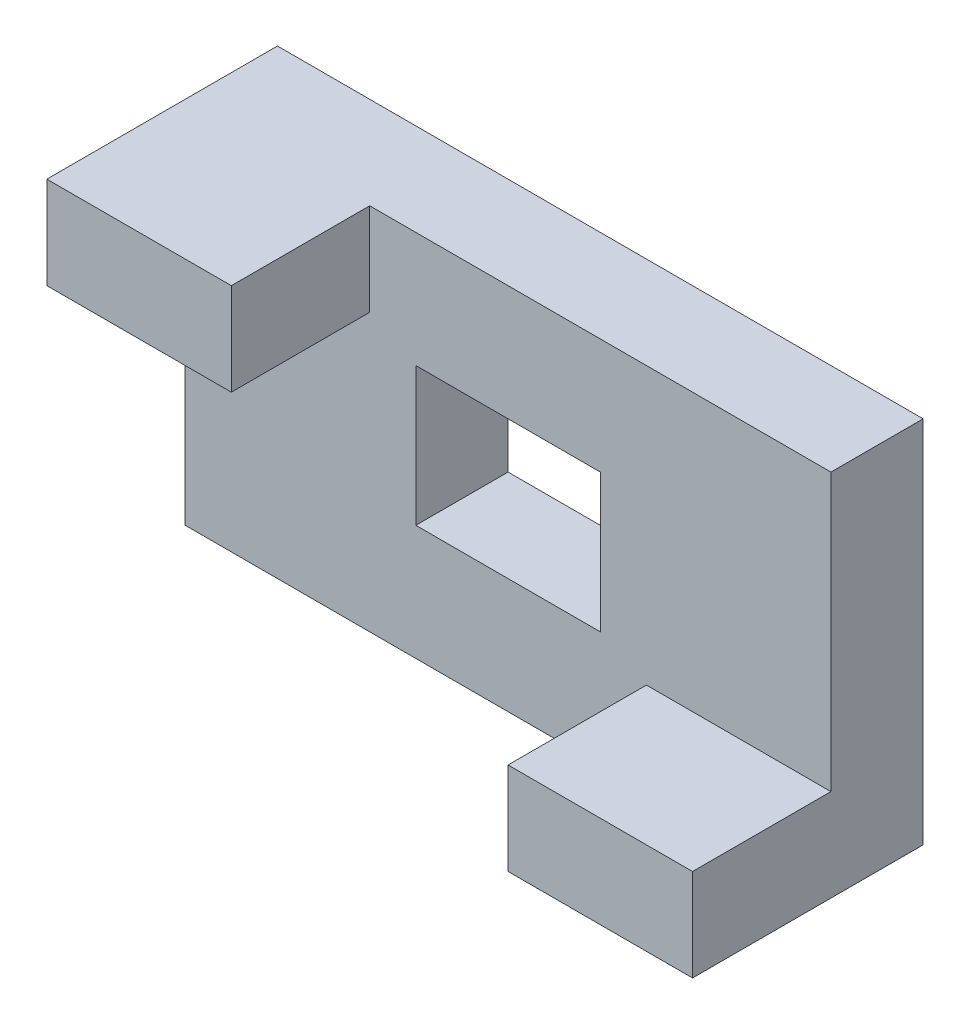
SolidWorks part; units mm, degrees
ref_plane "Front Plane" through (0, 0, 0) normal (0, 0, 1) x (1, 0, 0)
ref_plane "Top Plane" through (0, 0, 0) normal (0, 1, 0) x (1, 0, 0)
ref_plane "Right Plane" through (0, 0, 0) normal (1, 0, 0) x (0, 0, -1)
sketch "Sketch1" plane through (0, 0, 0) normal (0, 0, 1) x (1, 0, 0)
  line L0 (40, -32) -> (56, -32)
  line L1 (0, 0) -> (56, 0)
  line L2 (0, 0) -> (0, -32)
  line L3 (0, -32) -> (56, -32)
  line L4 (56, 0) -> (56, -32)
  line L5 (0, 0) -> (16, 0)
  line L6 (0, 0) -> (0, -8)
  line L7 (0, -8) -> (16, -8)
  line L8 (16, 0) -> (16, -8)
  line L9 (56, -24) -> (56, -32)
  line L10 (40, -24) -> (40, -32)
  line L11 (40, -24) -> (56, -24)
  line L13 (20, -10) -> (36, -10)
  line L14 (20, -10) -> (20, -22)
  line L15 (20, -22) -> (36, -22)
  line L16 (36, -10) -> (36, -22)
  point P12 (26.2336, -19.0655)
  dimension "D1" = 32
  dimension "D2" = 56
  dimension "D3" = 8
  dimension "D4" = 16
  dimension "D5" = 16
  dimension "D6" = 12
  dimension "D7" = 8
  dimension "D8" = 16
  dimension "D9" = 10
  dimension "D10" = 20
extrude "Boss-Extrude3" add sketch "Sketch1" along normal blind 8 contours L10 L11 L4 L1 L8 L7 L2 L3 L13 L16 L15 L14 region at (20, -31.355, 0)
extrude "Boss-Extrude4" add sketch "Sketch1<5>" along normal blind 20 contours L8 L1 L2 L7 | L11 L10 L0 L4 region at (48, -28, 0) region at (8, -4, 0)
sketch "Sketch1<5>" plane through (0, 0, 0) normal (0, 0, 1) x (1, 0, 0) same geometry as "Sketch1"
